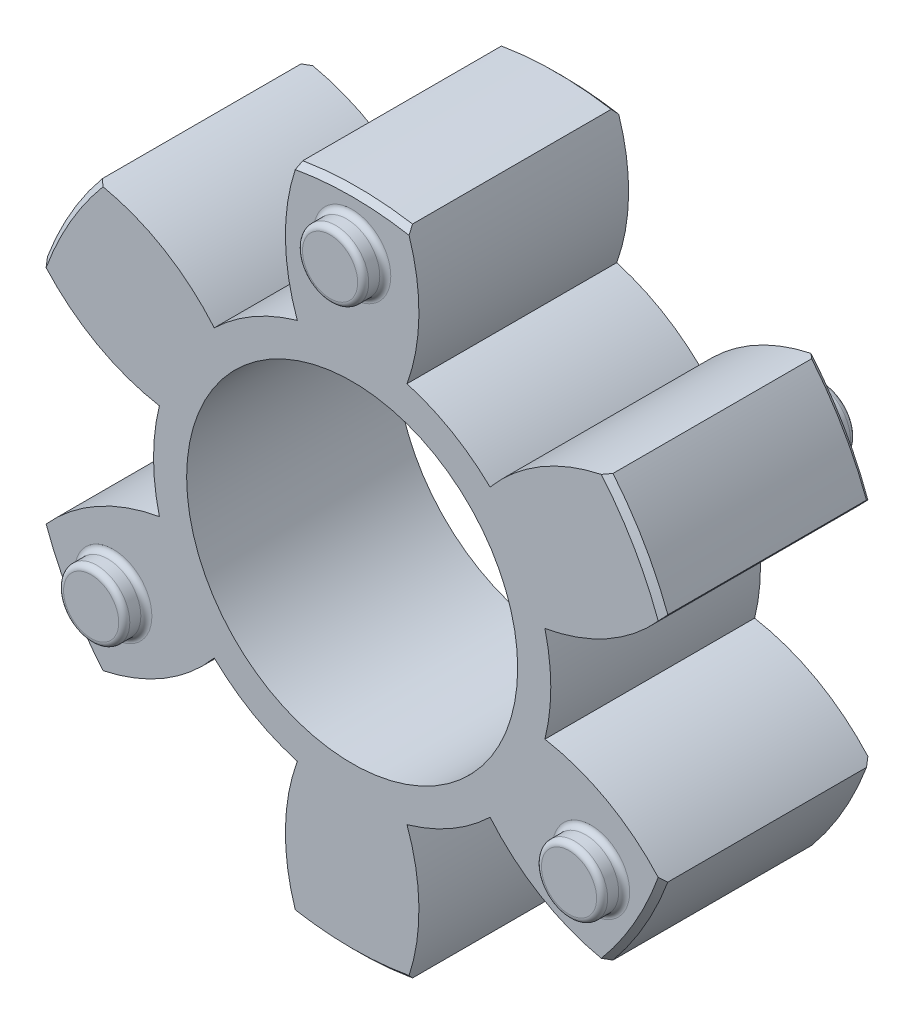
SolidWorks part; units mm, degrees
ref_plane "Front Plane" through (0, 0, 0) normal (0, 0, 1) x (1, 0, 0)
ref_plane "Top Plane" through (0, 0, 0) normal (0, 1, 0) x (1, 0, 0)
ref_plane "Right Plane" through (0, 0, 0) normal (1, 0, 0) x (0, 0, -1)
sketch "Sketch1" plane through (0, 0, 0) normal (0, 0, 1) x (1, 0, 0)
  line L0 (0, -15) -> (0, 15) construction
  line L1 (-3.6778, 12.5) -> (3.6778, 12.5) construction
  circle A0 centre (0, 0) radius 7.5
  arc A1 (-11.5684, 9.5484) -> (-14.0534, 5.2443) centre (0, 0) ccw
  arc A2 (-8.7337, 2.173) -> (-8.7337, -2.173) centre (0, 0) ccw
  circle A3 centre (0, 12.5) radius 1.5
  arc A4 (-2.485, 8.6501) -> (-2.485, 14.7927) centre (5.9747, 11.7214) cw
  arc A5 (2.485, 8.6501) -> (2.485, 14.7927) centre (-5.9747, 11.7214) ccw
  arc A6 (6.2487, 6.4771) -> (11.5684, 9.5484) centre (13.1384, 0.6864) cw
  arc A8 (8.7337, 2.173) -> (14.0534, 5.2443) centre (7.1637, 11.035) ccw
  arc A9 (8.7337, -2.173) -> (14.0534, -5.2443) centre (7.1637, -11.035) cw
  circle A10 centre (10.8253, -6.25) radius 1.5
  arc A11 (6.2487, -6.4771) -> (11.5684, -9.5484) centre (13.1384, -0.6864) ccw
  arc A12 (2.485, -8.6501) -> (2.485, -14.7927) centre (-5.9747, -11.7214) cw
  arc A14 (-2.485, -8.6501) -> (-2.485, -14.7927) centre (5.9747, -11.7214) ccw
  arc A15 (-6.2487, -6.4771) -> (-11.5684, -9.5484) centre (-13.1384, -0.6864) cw
  circle A16 centre (-10.8253, -6.25) radius 1.5
  arc A17 (-8.7337, -2.173) -> (-14.0534, -5.2443) centre (-7.1637, -11.035) ccw
  arc A18 (-8.7337, 2.173) -> (-14.0534, 5.2443) centre (-7.1637, 11.035) cw
  arc A20 (-6.2487, 6.4771) -> (-11.5684, 9.5484) centre (-13.1384, 0.6864) ccw
  circle A21 centre (-10.8253, 6.25) radius 1.5 [skipped]
  circle A22 centre (0, -12.5) radius 1.5 [skipped]
  circle A23 centre (10.8253, 6.25) radius 1.5 [skipped]
  arc A24 (-14.0534, -5.2443) -> (-11.5684, -9.5484) centre (0, 0) ccw
  arc A25 (-2.485, -14.7927) -> (2.485, -14.7927) centre (0, 0) ccw
  arc A26 (11.5684, -9.5484) -> (14.0534, -5.2443) centre (0, 0) ccw
  arc A27 (14.0534, 5.2443) -> (11.5684, 9.5484) centre (0, 0) ccw
  arc A28 (2.485, 14.7927) -> (-2.485, 14.7927) centre (0, 0) ccw
  arc A29 (-2.485, 8.6501) -> (-6.2487, 6.4771) centre (0, 0) ccw
  arc A30 (6.2487, 6.4771) -> (2.485, 8.6501) centre (0, 0) ccw
  arc A31 (8.7337, -2.173) -> (8.7337, 2.173) centre (0, 0) ccw
  arc A32 (2.485, -8.6501) -> (6.2487, -6.4771) centre (0, 0) ccw
  arc A33 (-6.2487, -6.4771) -> (-2.485, -8.6501) centre (0, 0) ccw
  point P3 (0, 0)
  point P8 (0, 0)
  point P11 (0, 12.5)
  point P19 (0, 0)
  point P20 (0, 0)
  point P62 (0, 0)
  dimension "D1" = 15
  dimension "D2" = 30
  dimension "D3" = 18
  dimension "D5" = 3
  dimension "D6" = 9
  dimension "D4" = 12.5
  dimension "D7" = 4.97
  dimension "D8" = 6
extrude "Boss-Extrude1" add sketch "Sketch1" along normal blind 9.5
extrude "Boss-Extrude2" add sketch "Sketch1<4>" along normal blind 10.5 contours A3 | A16 | A10 region at (0, 12.5, 0) region at (10.8253, -6.25, 0) region at (-10.8253, -6.25, 0)
sketch "Sketch1<4>" plane through (0, 0, 0) normal (0, 0, 1) x (1, 0, 0) same geometry as "Sketch1"
fillet "Fillet1" radius 0.25 6 edges at (12.3253, -6.25, 10.5) (1.5, 12.5, 10.5) (-9.3253, -6.25, 10.5) (1.5, 12.5, 9.5) (12.3253, -6.25, 9.5) (-9.3253, -6.25, 9.5)
chamfer "Chamfer1" distance 0.25 angle 45 12 edges at (12.9904, -7.5, 9.5) (0, -15, 9.5) (-12.9904, -7.5, 9.5) (-12.9904, 7.5, 9.5) (0, 15, 9.5) (12.9904, 7.5, 9.5) (-12.9904, 7.5, 0) (-12.9904, -7.5, 0) (0, -15, 0) (12.9904, -7.5, 0) (12.9904, 7.5, 0) (0, 15, 0)
sketch "Sketch2" plane through (0, 0, 0) normal (0, 0, -1) x (-1, 0, 0)
  line L0 (-14.4398, 0) -> (14.4398, 0) construction
  line L2 (0, -15) -> (0, 15) construction
  circle A0 centre (0, -12.5) radius 1.5
  circle A1 centre (0, 12.5) radius 1.5 construction
  circle A2 centre (-10.8253, 6.25) radius 1.5
  circle A3 centre (10.8253, 6.25) radius 1.5
  point P3 (0, 0)
  point P4 (0, 0)
  point P11 (0, 0)
  point P12 (0, 0)
  point P18 (0, 0)
  dimension "D1" = 12.5
  dimension "D3" = 12.5
  dimension "D2" = 3
extrude "Boss-Extrude3" add sketch "Sketch2" along normal blind 1
fillet "Fillet2" radius 0.25 6 edges at (1.5, -12.5, 0) (-1.5, -12.5, -1) (12.3253, 6.25, 0) (9.3253, 6.25, -1) (-9.3253, 6.25, 0) (-12.3253, 6.25, -1)
